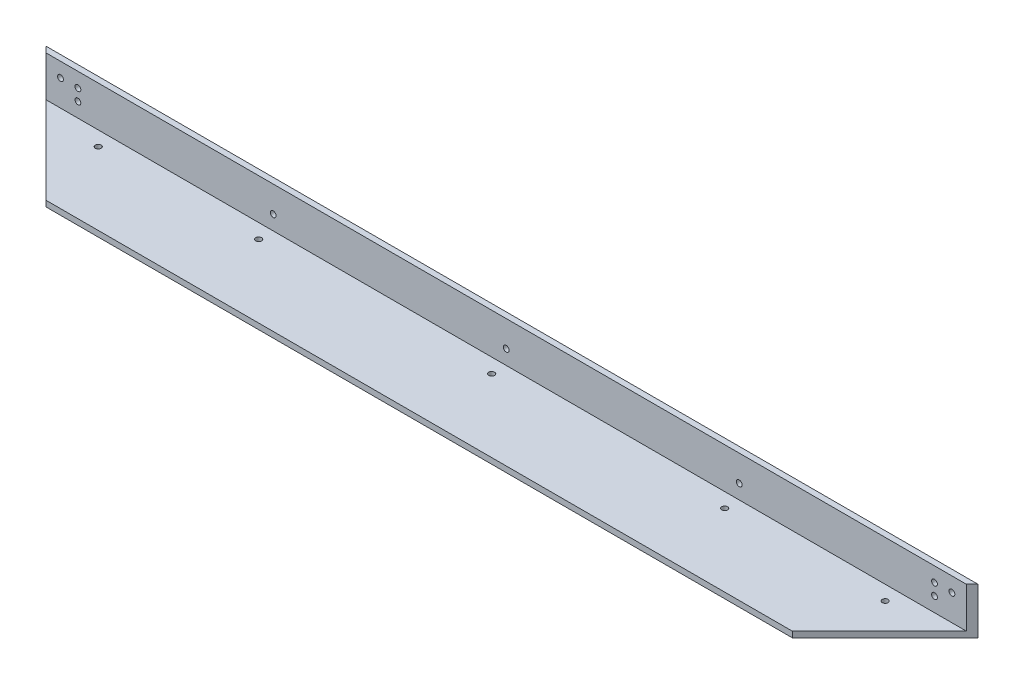
SolidWorks part; units mm, degrees
ref_plane "Front Plane" through (0, 0, 0) normal (0, 0, 1) x (1, 0, 0)
ref_plane "Top Plane" through (0, 0, 0) normal (0, 1, 0) x (1, 0, 0)
ref_plane "Right Plane" through (0, 0, 0) normal (1, 0, 0) x (0, 0, -1)
sketch "Sketch1" plane through (0, 0, 0) normal (1, 0, 0) x (0, 0, -1)
  line L0 (0, 0) -> (-50.8, 0)
  line L1 (-50.8, 0) -> (-50.8, 3.175)
  line L2 (-50.8, 3.175) -> (-3.175, 3.175)
  line L3 (-3.175, 3.175) -> (-3.175, 25.4)
  line L4 (-3.175, 25.4) -> (0, 25.4)
  line L5 (0, 25.4) -> (0, 0)
  dimension "LHeight" = 25.4
  dimension "LWidth" = 50.8
  dimension "LMaterialThickness" = 3.175
  dimension "D1" = 47.625
  dimension "D2" = 22.225
  dimension "D3" = 3.175
extrude "Boss-Extrude1" add sketch "Sketch1" along normal blind 510
chamfer "Chamfer6" distance 50.8 angle 45 1 edges at (510, 1.5875, 50.8)
chamfer "Chamfer7" distance 50.8 angle 45 1 edges at (0, 1.5875, 50.8)
sketch "BackSideHoles-Sketch2" plane through (0, 0, 0) normal (0, 0, -1) x (-1, 0, 0)
  line L0 (0, 0) -> (0, 25.4) construction
  line L1 (-510, 0) -> (0, 0) construction
  line L2 (-510, 0) -> (-510, 25.4) construction
  line L3 (-510, 25.4) -> (0, 25.4) construction
  circle A0 centre (-498.8875, 17.4625) radius 1.5875
  circle A1 centre (-489.3625, 17.4625) radius 1.5875
  circle A2 centre (-20.6375, 17.4625) radius 1.5875
  circle A4 centre (-11.1125, 17.4625) radius 1.5875
  circle A5 centre (-20.6375, 11.1125) radius 1.5875
  circle A6 centre (-489.3625, 11.1125) radius 1.5875
  circle A8 centre (-382.5, 11.1125) radius 1.5875
  circle A9 centre (-255, 11.1125) radius 1.5875
  circle A10 centre (-127.5, 11.1125) radius 1.5875
  dimension "D5" = 3.175
  dimension "D2" = 20.6375
  dimension "D4" = 20.6375
  dimension "D8" = 127.5
  dimension "D9" = 127.5
  dimension "D10" = 127.5
  dimension "D11" = 11.1125
  dimension "D6" = 7.9375
  dimension "D7" = 11.1125
  dimension "D3" = 11.1125
sketch "BottomHoles-Sketch3" plane through (0, 0, 0) normal (0, -1, 0) x (1, 0, 0)
  line L0 (510, 0) -> (0, 0) construction
  circle A7 centre (39.6875, 11.1125) radius 1.5875
  circle A8 centre (470.3125, 11.1125) radius 1.5875
  circle A9 centre (127.5, 11.1125) radius 1.5875
  circle A10 centre (255, 11.1125) radius 1.5875
  circle A11 centre (382.5, 11.1125) radius 1.5875
  dimension "D5" = 3.175
  dimension "D2" = 39.6875
  dimension "D3" = 39.6875
  dimension "D4" = 11.1125
  dimension "D1" = 127.5
  dimension "D6" = 127.5
  dimension "D7" = 127.5
extrude "BottomHoles-Cut-Extrude1" cut sketch "BottomHoles-Sketch3" against normal through all
extrude "BackSideHoles-Cut-Extrude2" cut sketch "BackSideHoles-Sketch2" against normal through all
equation "\"LowerRailWidth\"= 2.00in"
equation "\"LowerRailHeight\"= 1.00in"
equation "\"RailThickness\"= .125in'Spec"
equation "\"SideRailHoleX1FromSide\"= \"HoleOffsetFromSide\""
equation "\"SideRailHoleX2FromSide\"= \"VSWidth\" - \"HoleOffsetFromEdge\" - \"RailThickness\"'Equals 20.6375"
equation "\"SideRailHoleY1FromEdge\"= \"HoleOffsetFromEdge\""
equation "\"FrontBackRailLength\"= 510mm"
equation "\"VSWidth\"= 1.25in'Spec"
equation "\"HoleOffsetFromEdge\"= \"RailThickness\" * 2.5"
equation "\"HoleOffsetFromSide\"= \"RailThickness\" * 3.5"
equation "\"SideRailHoleY2FromSide\"= \"HoleOffsetFromSide\""
equation "\"FasteningHoleDiameter\"= .125in"
equation "\"D1@Boss-Extrude1\"=\"FrontBackRailLength\""
equation "\"D1@Chamfer6\"=\"LowerRailWidth\""
equation "\"D1@Chamfer7\"=\"LowerRailWidth\""
equation "\"D2@BackSideHoles-Sketch2\" = \"SideRailHoleX2FromSide\""
equation "\"D4@BackSideHoles-Sketch2\" = \"SideRailHoleX2FromSide\""
equation "\"D5@BackSideHoles-Sketch2\" = \"FasteningHoleDiameter\""
equation "\"LHeight@Sketch1\"=\"LowerRailHeight\""
equation "\"LWidth@Sketch1\"=\"LowerRailWidth\""
equation "\"24vPSUMountingHoleDistanceFromEdge\"= 33.5mm"
equation "\"24vPSUMountingHoleDistance\"= 150mm"
equation "\"24vPSUMountingHoleDiameter\"= 2.5mm"
equation "\"LowerCornerBlockWidth\"= \"LowerRailWidth\" - \"RailThickness\" * 2'Room for left front stepper"
equation "\"D2@BottomHoles-Sketch3\"=\"LowerCornerBlockX1FromSide\""
equation "\"D3@BottomHoles-Sketch3\"=\"LowerCornerBlockX1FromSide\""
equation "\"D4@BottomHoles-Sketch3\"=\"LowerCornerBlockY1FromSide\""
equation "\"D5@BottomHoles-Sketch3\"=\"FasteningHoleDiameter\""
equation "\"LowerCornerBlockX1FromSide\"= \"LowerCornerBlockWidth\" - \"HoleOffsetFromEdge\" + \"RailThickness\""
equation "\"LowerCornerBlockY1FromSide\"= \"HoleOffsetFromSide\""
equation "\"FrontOrBackEnclosureOffsets\"= \"FrontBackRailLength\" / 4"
equation "\"D1@BottomHoles-Sketch3\"=\"FrontOrBackEnclosureOffsets\""
equation "\"D6@BottomHoles-Sketch3\"=\"FrontOrBackEnclosureOffsets\""
equation "\"D7@BottomHoles-Sketch3\"=\"FrontOrBackEnclosureOffsets\""
equation "\"D8@BackSideHoles-Sketch2\"=\"FrontOrBackEnclosureOffsets\""
equation "\"D9@BackSideHoles-Sketch2\"=\"FrontOrBackEnclosureOffsets\""
equation "\"D10@BackSideHoles-Sketch2\"=\"FrontOrBackEnclosureOffsets\""
equation "\"D11@BackSideHoles-Sketch2\"=\"SideRailHoleX1FromSide\""
equation "\"D6@BackSideHoles-Sketch2\"=\"SideRailHoleY1FromEdge\""
equation "\"D7@BackSideHoles-Sketch2\"=\"SideRailHoleY2FromSide\""
equation "\"D3@BackSideHoles-Sketch2\"=\"SideRailHoleX1FromSide\""
